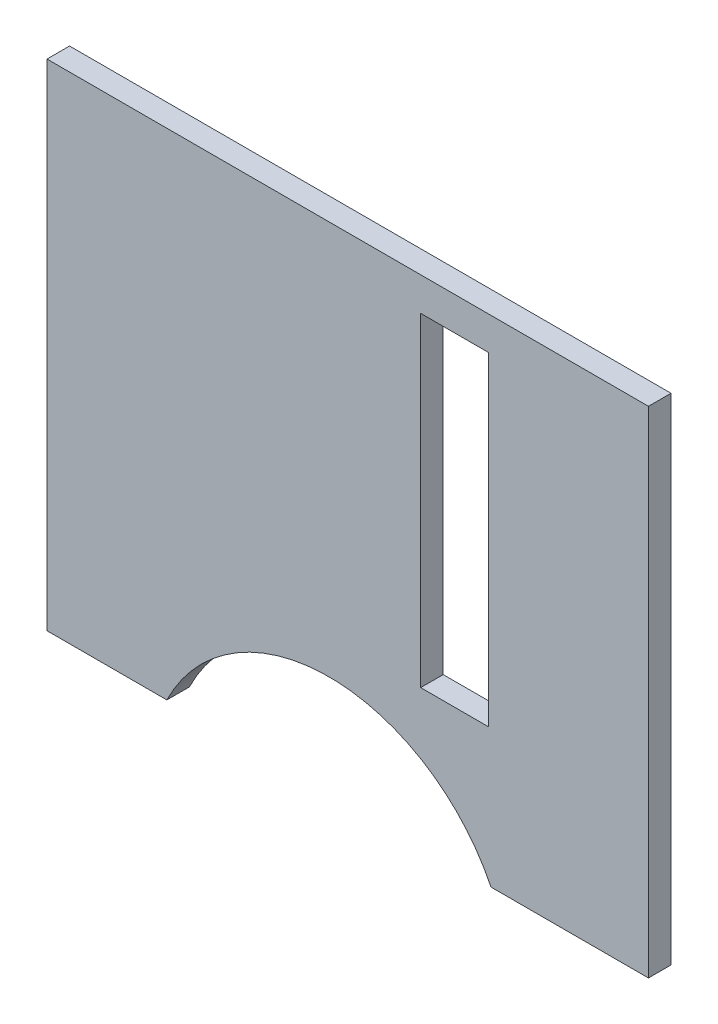
SolidWorks part; units mm, degrees
ref_plane "Front Plane" through (0, 0, 0) normal (0, 0, 1) x (1, 0, 0)
ref_plane "Top Plane" through (0, 0, 0) normal (0, 1, 0) x (1, 0, 0)
ref_plane "Right Plane" through (0, 0, 0) normal (1, 0, 0) x (0, 0, -1)
sketch "Sketch1" plane through (0, 0, 0) normal (0, 0, 1) x (1, 0, 0)
  line L0 (0, -65.857) -> (15.9432, -65.857)
  line L1 (0, 0) -> (80, 0)
  line L2 (0, 0) -> (0, -65.857)
  line L3 (0, -65.857) -> (80, -65.857) construction
  line L4 (80, 0) -> (80, -65.857)
  line L5 (49.7, -4.4432) -> (58.7, -4.4432)
  line L6 (49.7, -4.4432) -> (49.7, -47.5568)
  line L7 (49.7, -47.5568) -> (58.7, -47.5568)
  line L8 (58.7, -4.4432) -> (58.7, -47.5568)
  line L9 (59.0568, -65.857) -> (80, -65.857)
  circle A0 centre (37.5, -76.407) radius 21 construction
  arc A1 (59.0568, -65.857) -> (15.9432, -65.857) centre (37.5, -76.407) ccw
  circle A2 centre (37.5, -76.407) radius 21 construction
  dimension "D1" = 3
sketch "Sketch2" plane through (0, 0, 0) normal (0, 1, 0) x (1, 0, 0)
  line L1 (80, 0) -> (0, 0)
  line L2 (80, 0) -> (80, 3)
  line L3 (80, 3) -> (0, 3)
  line L4 (0, 0) -> (0, 3)
extrude "Boss-Extrude1" add sketch "Sketch1" against normal up to vertex (3 mm away) up to point (0, 0, -3)
